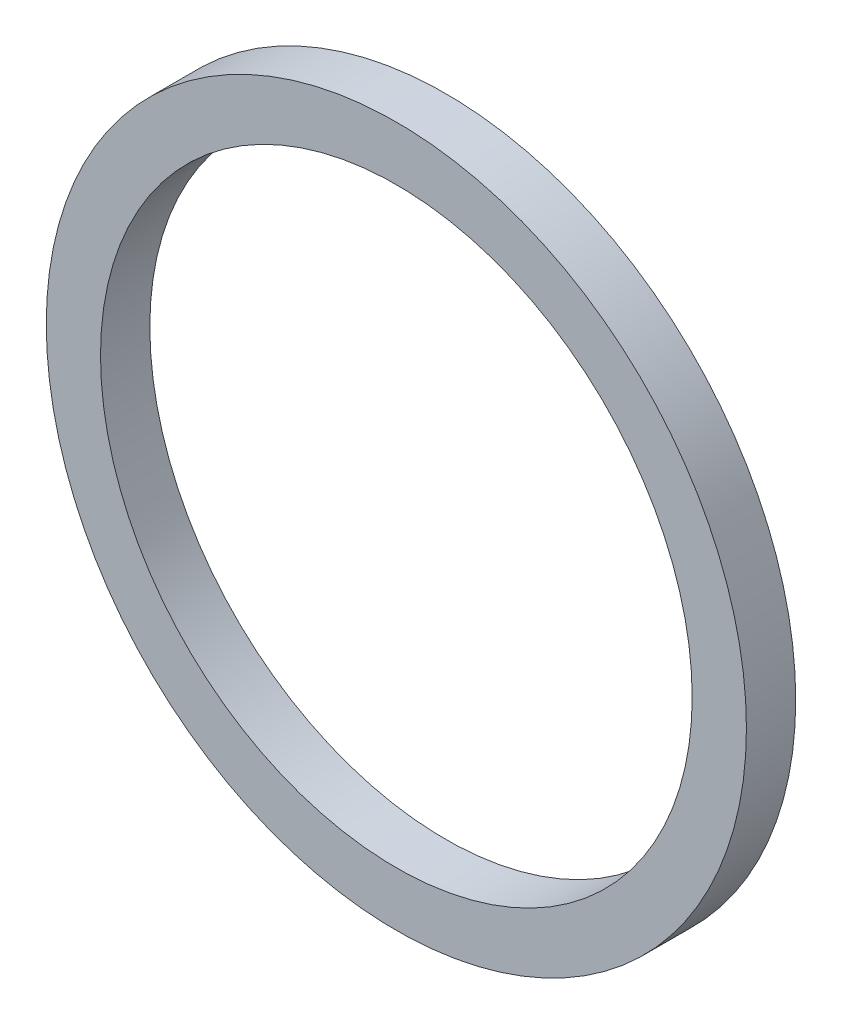
SolidWorks part; units mm, degrees
material "Plain Carbon Steel"
ref_plane "Front Plane" through (0, 0, 0) normal (0, 0, 1) x (1, 0, 0)
ref_plane "Top Plane" through (0, 0, 0) normal (0, 1, 0) x (1, 0, 0)
ref_plane "Right Plane" through (0, 0, 0) normal (1, 0, 0) x (0, 0, -1)
sketch "Sketch1" plane through (0, 0, 0) normal (0, 0, 1) x (1, 0, 0)
  circle A0 centre (0, 0) radius 22.5425
  circle A1 centre (0, 0) radius 19.05
  dimension "D1" = 45.085
  dimension "D2" = 38.1
extrude "Boss-Extrude1" add sketch "Sketch1" along normal blind 3.175
